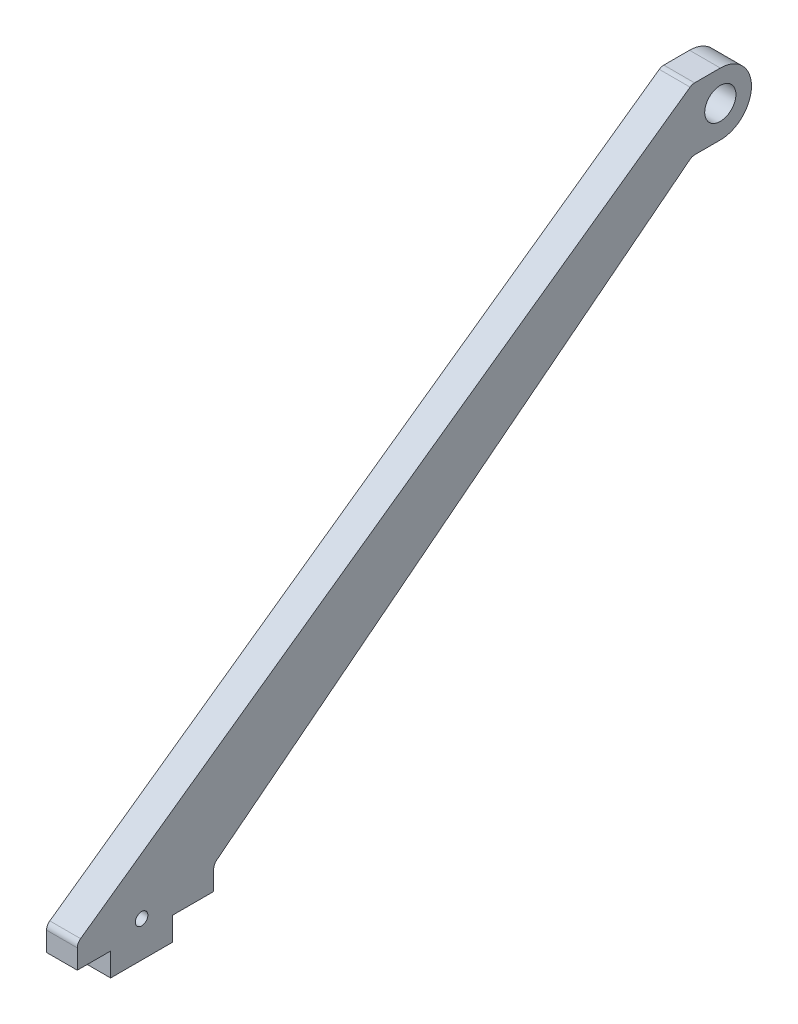
SolidWorks part; units mm, degrees
ref_plane "Plan de face" through (0, 0, 0) normal (0, 0, 1) x (1, 0, 0)
ref_plane "Plan de dessus" through (0, 0, 0) normal (0, 1, 0) x (1, 0, 0)
ref_plane "Plan de droite" through (0, 0, 0) normal (1, 0, 0) x (0, 0, -1)
sketch "Esquisse1" plane through (0, 0, 0) normal (1, 0, 0) x (0, 0, -1)
  line L0 (37.9609, 0.9844) -> (37.9609, 6.9844)
  line L1 (37.9609, 6.9844) -> (29.4109, 6.9844)
  line L2 (37.9609, 0.9844) -> (53.8609, 0.9844)
  line L3 (53.8609, 0.9844) -> (53.8609, 6.9844)
  line L4 (53.8609, 6.9844) -> (64.4109, 6.9844)
  line L5 (187.1755, 124.9844) -> (29.4109, 12.9844)
  line L6 (64.4109, 6.9844) -> (64.4109, 12.9844)
  line L7 (194.4109, 124.9844) -> (187.1755, 124.9844)
  line L8 (194.4109, 108.9844) -> (187.1755, 108.9844)
  line L9 (64.4109, 12.9844) -> (187.1755, 108.9844)
  line L10 (29.4109, 12.9844) -> (29.4109, 6.9844)
  arc A1 (194.4109, 124.9844) -> (194.4109, 108.9844) centre (194.4109, 116.9844) cw
  dimension "D5" = 10.55
  dimension "D8" = 130
  dimension "D1" = 15.9
  dimension "D2" = 6
  dimension "D3" = 6
  dimension "D6" = 6
  dimension "D7" = 8.55
  dimension "D9" = 110
  dimension "D11" = 16
extrude "Boss.-Extru.1" add sketch "Esquisse1" along normal blind 7.9 contours L1 L10 L5 L7 A1 L8 L9 L6 L4 L3 L2 L0
sketch "Esquisse2" plane through (7.9, 0, 0) normal (1, 0, 0) x (0, 0, -1)
  line L0 (37.9609, 0.9844) -> (53.8609, 0.9844) construction
  line L2 (64.4109, 6.9844) -> (64.4109, 12.9844) construction
  circle A0 centre (45.9109, 10.1844) radius 1.6
  circle A1 centre (194.4109, 117.1189) radius 4
  dimension "D1" = 9.2
  dimension "D2" = 3.2
  dimension "D4" = 8
  dimension "D3" = 18.5
extrude "Enlèv. mat.-Extru.1" cut sketch "Esquisse2" against normal through all
fillet "Congé1" radius 2 4 edges at (3.95, 12.9844, -29.4109) (3.95, 12.9844, -64.4109) (3.95, 108.9844, -187.1755) (3.95, 124.9844, -187.1755)
